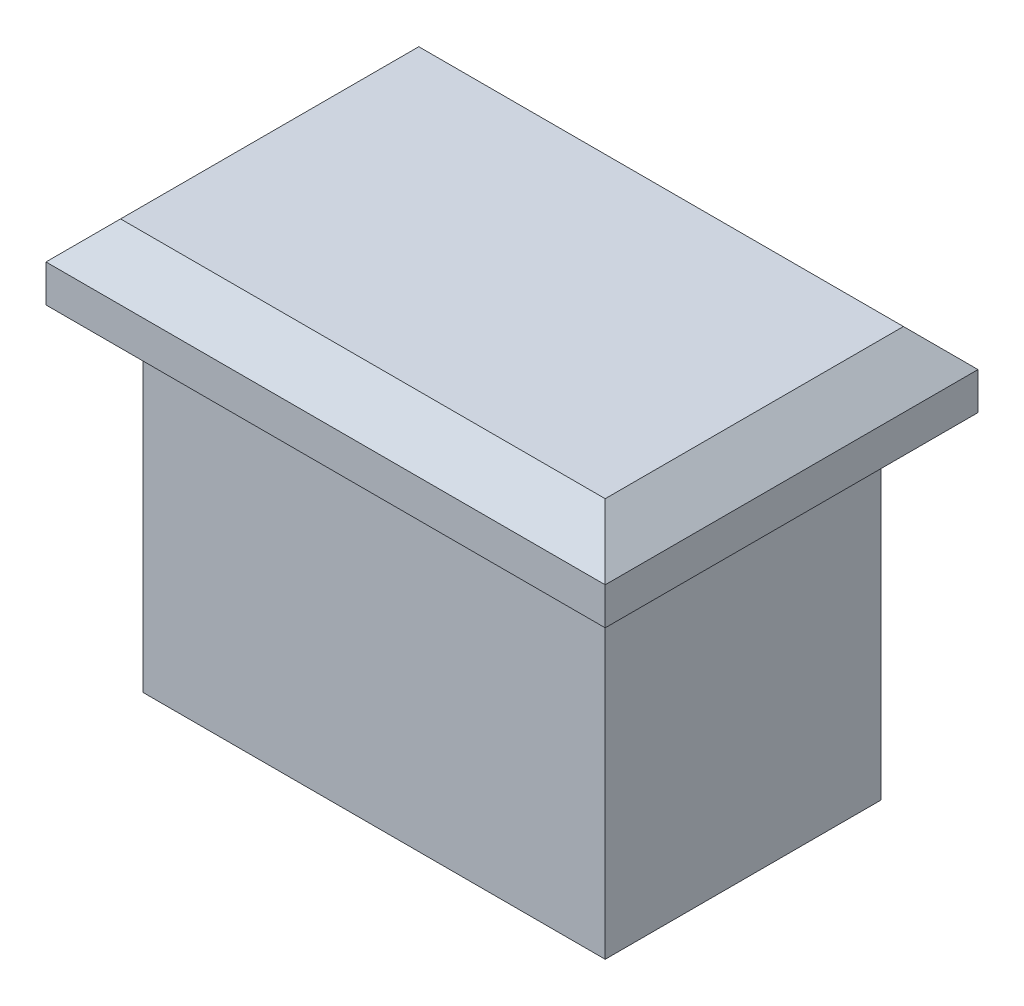
SolidWorks part; units mm, degrees
ref_plane "正面" through (0, 0, 0) normal (0, 0, 1) x (1, 0, 0)
ref_plane "平面" through (0, 0, 0) normal (0, 1, 0) x (1, 0, 0)
ref_plane "右側面" through (0, 0, 0) normal (1, 0, 0) x (0, 0, -1)
sketch "ｽｹｯﾁ1" plane through (0, 0, 0) normal (0, 1, 0) x (1, 0, 0)
  line L0 (-6.2, 3.7) -> (6.2, 3.7)
  line L5 (-7.5, 5) -> (7.5, 5)
  line L6 (-7.5, 5) -> (-7.5, -5)
  line L7 (-7.5, -5) -> (7.5, -5)
  line L8 (7.5, 5) -> (7.5, -5)
  line L9 (-7.5, 5) -> (7.5, -5) construction
  line L10 (-7.5, -5) -> (7.5, 5) construction
  line L11 (6.2, 3.7) -> (6.2, -3.7)
  line L12 (-6.2, -3.7) -> (6.2, -3.7)
  line L13 (-6.2, 3.7) -> (-6.2, -3.7)
  point P0 (0, 0)
  dimension "D1" = 10
  dimension "D2" = 15
  dimension "D3" = 1.3
extrude "ﾎﾞｽ - 押し出し1" add sketch "ｽｹｯﾁ1" along normal blind 2 contours L0 L13 L12 L11 | L8 L5 L6 L7 L13 L0 L11 L12 region at (0, 0, 0) region at (0, 0, -4.8197)
sketch "ｽｹｯﾁ2" plane through (0, 0, 0) normal (0, -1, 0) x (1, 0, 0)
  line L4 (-7.5, -5) -> (7.5, -5)
  line L5 (7.5, -5) -> (7.5, 5)
  line L6 (7.5, 5) -> (-7.5, 5)
  line L7 (-7.5, 5) -> (-7.5, -5)
  line L8 (-7.5, -5) -> (7.5, -5)
  line L9 (7.5, -5) -> (7.5, 5)
  line L10 (7.5, 5) -> (-7.5, 5)
  line L11 (-7.5, 5) -> (-7.5, -5)
  line L12 (-6.2, -3.7) -> (6.2, -3.7)
  line L13 (6.2, -3.7) -> (6.2, 3.7)
  line L14 (6.2, 3.7) -> (-6.2, 3.7)
  line L15 (-6.2, 3.7) -> (-6.2, -3.7)
  line L16 (-6.2, -3.7) -> (6.2, -3.7)
  line L17 (6.2, -3.7) -> (6.2, 3.7)
  line L18 (6.2, 3.7) -> (-6.2, 3.7)
  line L19 (-6.2, 3.7) -> (-6.2, -3.7)
  dimension "D1" = 0
  dimension "D2" = 0
extrude "ﾎﾞｽ - 押し出し2" add sketch "ｽｹｯﾁ2" along normal blind 10 contours L18 L19 L16 L17 region at (0, 0, 0)
chamfer "面取り1" distance 1 angle 45 4 edges at (6.2, -10, 0) (0, -10, -3.7) (-6.2, -10, 0) (0, -10, 3.7)
chamfer "面取り2" distance 1 angle 45 4 edges at (0, 2, 5) (-7.5, 2, 0) (0, 2, -5) (7.5, 2, 0)
